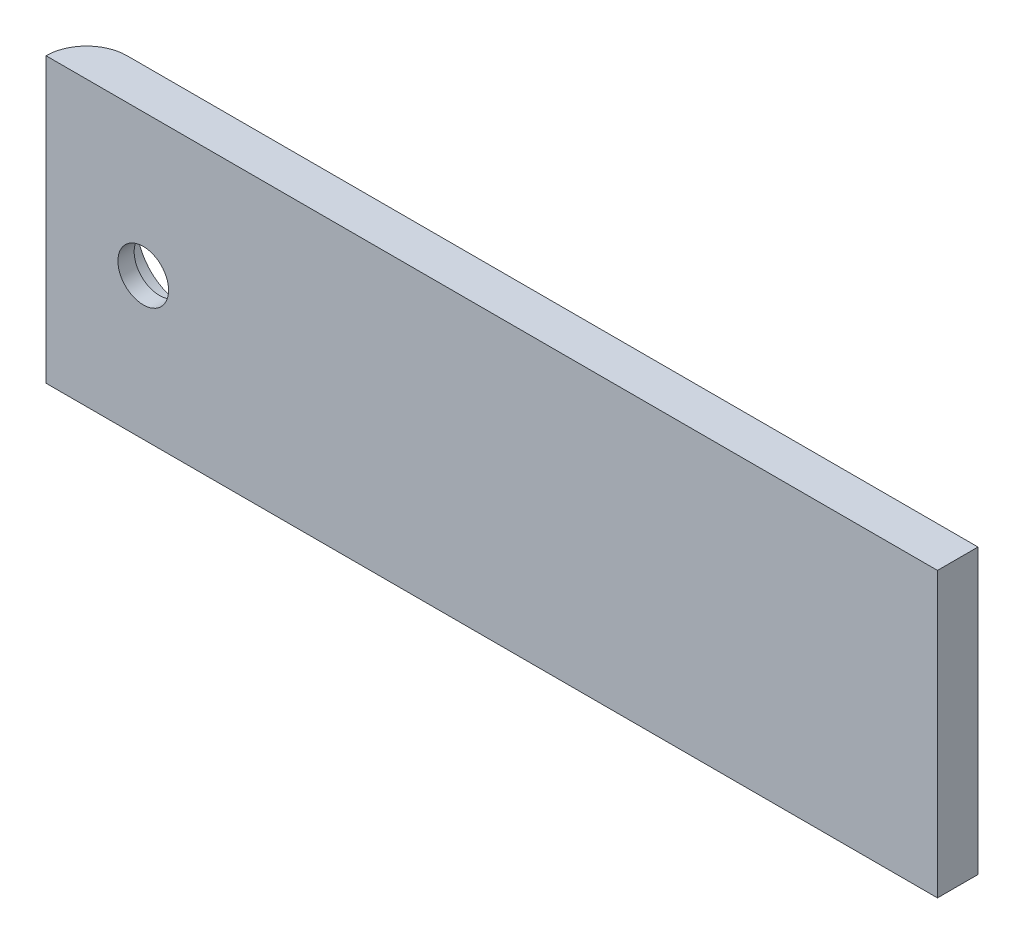
SolidWorks part; units mm, degrees
material "PE High Density"
ref_plane "Front Plane" through (0, 0, 0) normal (0, 0, 1) x (1, 0, 0)
ref_plane "Top Plane" through (0, 0, 0) normal (0, 1, 0) x (1, 0, 0)
ref_plane "Right Plane" through (0, 0, 0) normal (1, 0, 0) x (0, 0, -1)
sketch "Sketch1" plane through (0, 0, 0) normal (0, 1, 0) x (1, 0, 0)
  line L1 (0, 0) -> (139.7, 0)
  line L2 (0, 0) -> (0, 6.35)
  line L3 (0, 6.35) -> (139.7, 6.35)
  line L4 (139.7, 0) -> (139.7, 6.35)
  dimension "D1" = 139.7
  dimension "D2" = 6.35
extrude "Boss-Extrude1" add sketch "Sketch1" along normal blind 44.45
fillet "Fillet1" radius 6.35 1 edges at (0, 22.225, -6.35)
extrude "Cut-Extrude2" cut sketch "Sketch4" against normal blind 254
sketch "Sketch4" plane through (69.9488, 1.4152, 139.7) normal (0, 0, 1) x (1, 0, 0)
  circle A0 centre (-54.7088, 20.8098) radius 3.9687
sketch "Sketch6" plane through (0, 0, -6.35) normal (0, 0, -1) x (-1, 0, 0)
  circle A1 centre (-15.24, 22.225) radius 7.3323
extrude "Cut-Extrude4" cut sketch "Sketch6" against normal blind 3.81
